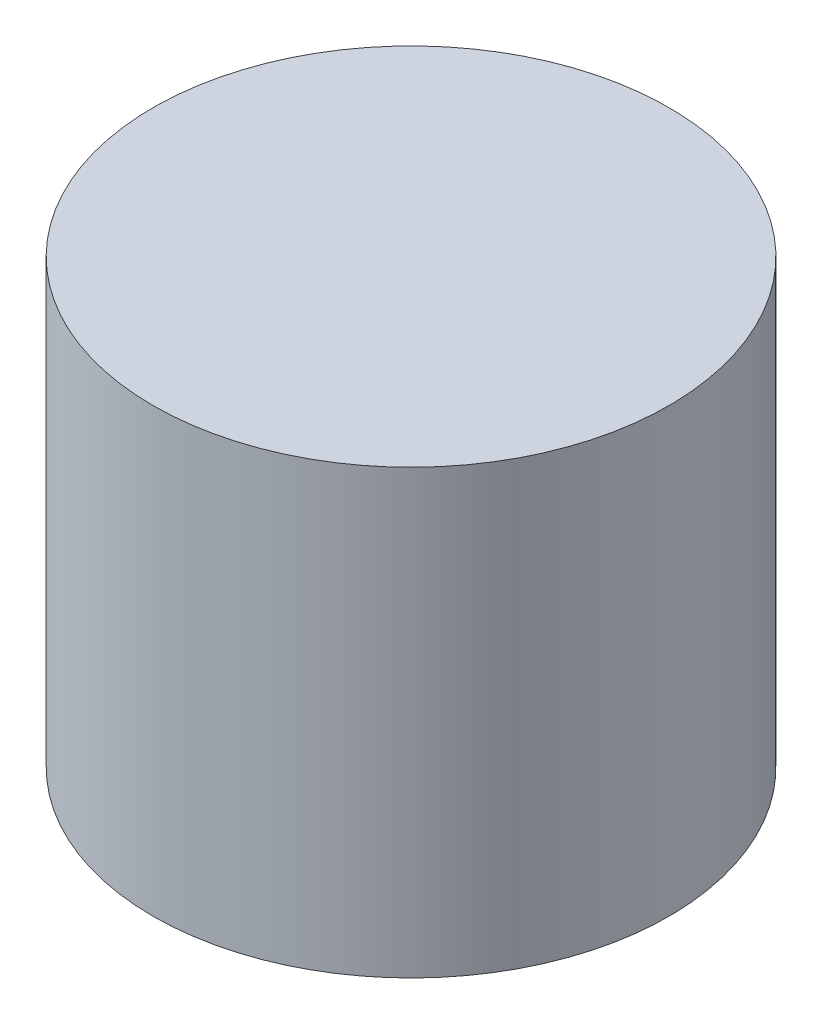
SolidWorks part; units mm, degrees
ref_plane "Front Plane" through (0, 0, 0) normal (0, 0, 1) x (1, 0, 0)
ref_plane "Top Plane" through (0, 0, 0) normal (0, 1, 0) x (1, 0, 0)
ref_plane "Right Plane" through (0, 0, 0) normal (1, 0, 0) x (0, 0, -1)
sketch "Sketch1" plane through (0, 0, 0) normal (0, 1, 0) x (1, 0, 0)
  circle A0 centre (0, 0) radius 7
  dimension "D1" = 14
extrude "Boss-Extrude1" add sketch "Sketch1" along normal blind 12
sketch "Sketch2" plane through (0, 0, 0) normal (0, -1, 0) x (1, 0, 0)
  line L0 (-2.75, -1) -> (2.75, -1)
  circle A1 centre (0, 0) radius 2.9262 construction
  arc A2 (-2.75, -1) -> (2.75, -1) centre (0, 0) cw
  point P2 (0, -1)
  dimension "D2" = 1
  dimension "D1" = 5.5
extrude "Cut-Extrude1" cut sketch "Sketch2" against normal blind 5
